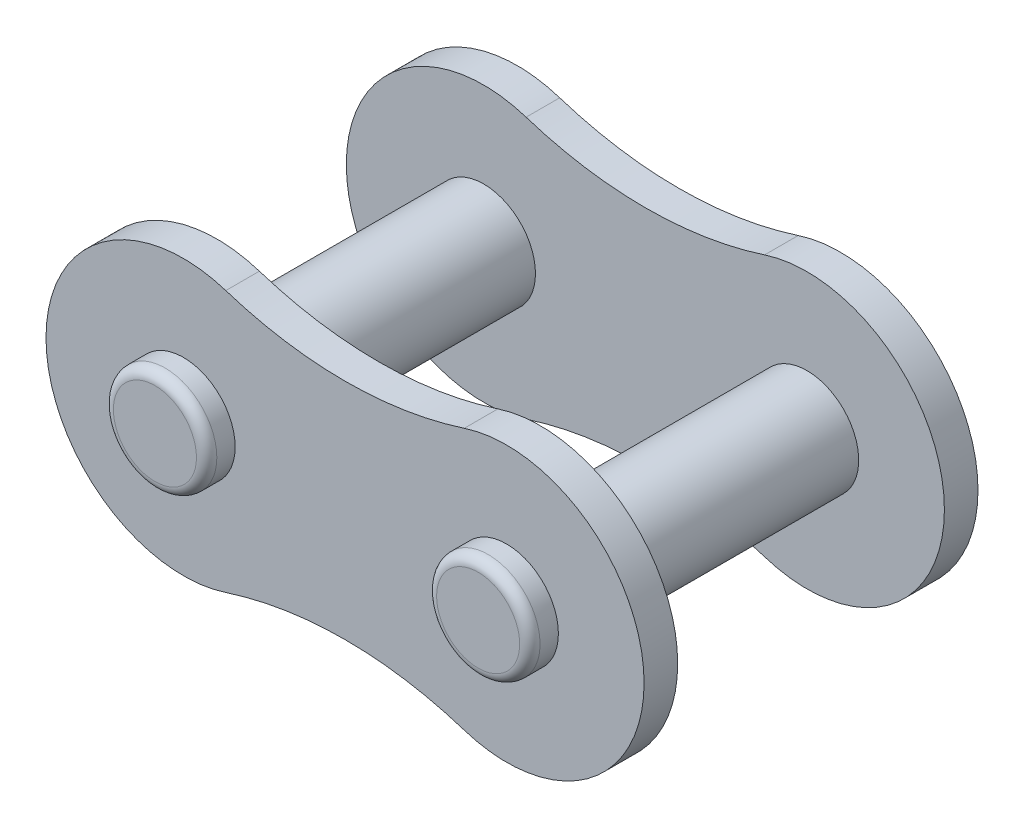
SolidWorks part; units mm, degrees
ref_plane "Front Plane" through (0, 0, 0) normal (0, 0, 1) x (1, 0, 0)
ref_plane "Top Plane" through (0, 0, 0) normal (0, 1, 0) x (1, 0, 0)
ref_plane "Right Plane" through (0, 0, 0) normal (1, 0, 0) x (0, 0, -1)
ref_axis "Axis_X" through (-24.0938, 0, 0) along (1, 0, 0)
ref_axis "Axis_Y" through (0, 7.425, 0) along (0, -1, 0)
ref_axis "Axis_Z" through (0, 0, -10.56) along (0, 0, 1)
sketch "Sketch1" plane through (0, 0, 0) normal (0, 1, 0) x (1, 0, 0)
  line L0 (0, 0) -> (0, 9.6) construction
  line L1 (0, -9.6) -> (0, 9.6)
  line L2 (0, 9.6) -> (2.04, 9.6)
  line L3 (2.54, 9.1) -> (2.54, -9.1)
  line L4 (2.04, -9.6) -> (0, -9.6)
  line L5 (0, 0) -> (2.54, 0) construction
  arc A0 (2.54, 9.1) -> (2.04, 9.6) centre (2.04, 9.1) ccw
  arc A1 (2.04, -9.6) -> (2.54, -9.1) centre (2.04, -9.1) ccw
  point P9 (2.54, 9.6)
  dimension "FIX_52" = 0.5
  dimension "FIX_53" = 0.5
  dimension "FIX_51" = 5.08
  dimension "FIX_54" = 19.2
revolve "Revolve1" add sketch "Sketch1" angle 360 about axis through (0, 0, -10.56) along (0, 0, 1)
sketch "Sketch2" plane through (0, 0, 0) normal (0, -1, 0) x (1, 0, 0)
  line L0 (-15.875, 9.6) -> (-15.875, -9.6) construction
  line L1 (-15.875, 9.6) -> (-17.915, 9.6)
  line L2 (-18.415, 9.1) -> (-18.415, -9.1)
  line L3 (-17.915, -9.6) -> (-15.875, -9.6)
  line L4 (-15.875, -9.6) -> (-15.875, 9.6)
  line L5 (0, 0) -> (-15.875, 0) construction
  arc A0 (-18.415, -9.1) -> (-17.915, -9.6) centre (-17.915, -9.1) ccw
  arc A1 (-18.415, 9.1) -> (-17.915, 9.6) centre (-17.915, 9.1) cw
  dimension "FIX_57" = 0.5
  dimension "FIX_59" = 0.5
  dimension "FIX_56" = 5.08
  dimension "FIX_58" = 15.875
  dimension "FIX_60" = 19.2
revolve "Revolve2" add sketch "Sketch2" angle 360 about L0
ref_plane "Plane1" through (0, 0, -6.55) normal (0, 0, 1) x (1, 0, 0)
sketch "Sketch3" plane through (0, 0, -6.55) normal (0, 0, -1) x (0, -1, 0)
  line L0 (0, 0) -> (0, 15.875) construction
  line L1 (-6.75, 0) -> (6.75, 0) construction
  arc A0 (-6.4213, 2.0807) -> (6.4213, 2.0807) centre (0, 0) ccw
  arc A1 (6.4213, 13.7943) -> (-6.4213, 13.7943) centre (0, 15.875) ccw
  circle A2 centre (0, 0) radius 2.54
  circle A3 centre (0, 15.875) radius 2.54
  arc A4 (6.4213, 13.7943) -> (6.4213, 2.0807) centre (24.4961, 7.9375) ccw
  arc A5 (-6.4213, 13.7943) -> (-6.4213, 2.0807) centre (-24.4961, 7.9375) cw
  dimension "FIX_63" = 5.08
  dimension "FIX_64" = 19
  dimension "FIX_65" = 13.5
extrude "Boss-Extrude1" add sketch "Sketch3" along normal blind 1.65
mirror "Mirror1" about plane through (0, 0, 0) normal (0, 0, 1) of "Boss-Extrude1"
equation "\"Factor\"= 1.082532"
